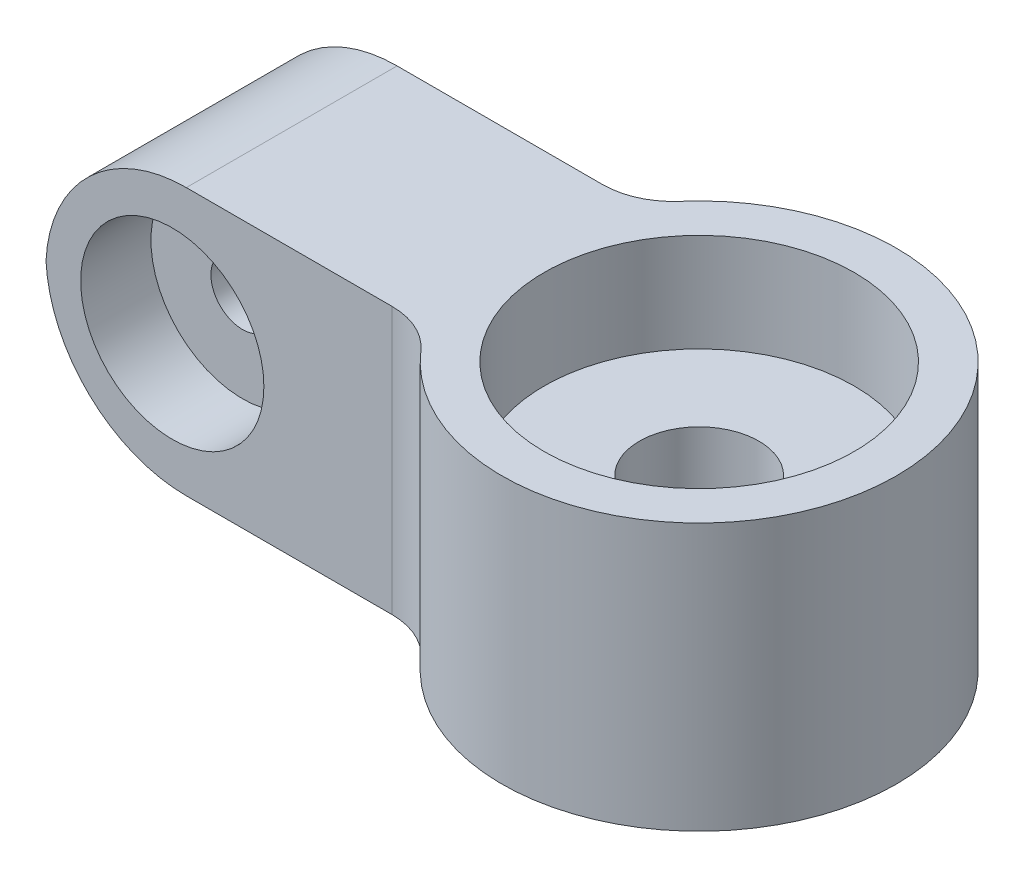
SolidWorks part; units mm, degrees
ref_plane "Front Plane" through (0, 0, 0) normal (0, 0, 1) x (1, 0, 0)
ref_plane "Top Plane" through (0, 0, 0) normal (0, 1, 0) x (1, 0, 0)
ref_plane "Right Plane" through (0, 0, 0) normal (1, 0, 0) x (0, 0, -1)
sketch "Sketch1" plane through (0, 0, 0) normal (0, 0, 1) x (1, 0, 0)
  line L0 (0, 0) -> (39, 0) construction
  line L1 (0, -9.5) -> (39, -9.5)
  line L2 (0, -9.5) -> (0, 9.5)
  line L3 (0, 9.5) -> (39, 9.5)
  line L4 (39, -9.5) -> (39, 9.5)
  circle A0 centre (9, 0) radius 6.52
  circle A1 centre (9, 0) radius 2.25
  dimension "D2" = 19
  dimension "R_625z" = 13.04
  dimension "D4" = 4.5
  dimension "D1" = 30
  dimension "D3" = 9
extrude "Boss-Extrude1" add sketch "Sketch1" along normal mid plane 15 contours A0 L0 A1 | L2 L0 A0 L4 L3 | L0 L2 L1 L4 A0 | L0 A0 A1 region at (9, 3.0122, 0) region at (9, -3.0122, 0) region at (21.8085, 5.1859, 0) region at (21.8085, -5.1859, 0)
extrude "Cortar-Extruir1" cut sketch "Sketch1<3>" against normal blind 5 from surface contours A0 starting at face at (19.5, 0, 7.5)
sketch "Sketch1<3>" plane through (0, 0, 0) normal (0, 0, 1) x (1, 0, 0) same geometry as "Sketch1"
extrude "Cortar-Extruir2" cut sketch "Sketch1<5>" along normal blind 5 from surface contours A0 starting at face at (19.5, 0, -7.5)
sketch "Sketch1<5>" plane through (0, 0, 0) normal (0, 0, 1) x (1, 0, 0) same geometry as "Sketch1"
sketch "Sketch2" plane through (0, 0, 0) normal (0, 1, 0) x (1, 0, 0)
  line L0 (39, -7.5) -> (39, 7.5) construction
  circle A0 centre (39, 0) radius 11.04
  circle A1 centre (39, 0) radius 14.04
  circle A2 centre (39, 0) radius 4.25
  dimension "D1" = 22.08
  dimension "D3" = 8.5
  dimension "D2" = 3
extrude "Boss-Extrude3" add sketch "Sketch2" against normal through all and the other way through all contours A0 | A1 A0 | A1 A0 | A0 region at (28.2723, 0, 0) region at (25.3571, 0, 0)
extrude "Cortar-Extruir3" cut sketch "Sketch2<4>" along normal blind 7 from surface contours A0 starting at face at (20.0428, -9.5, 0)
sketch "Sketch2<4>" plane through (0, 0, 0) normal (0, 1, 0) x (1, 0, 0) same geometry as "Sketch2"
extrude "Cortar-Extruir4" cut sketch "Sketch2<5>" against normal blind 7 from surface contours A0 starting at face at (41.125, 9.5, 0)
sketch "Sketch2<5>" plane through (0, 0, 0) normal (0, 1, 0) x (1, 0, 0) same geometry as "Sketch2"
extrude "Cortar-Extruir5" cut sketch "Sketch2<6>" against normal through all both and the other way through all contours A2 region at (39, 0, 0)
sketch "Sketch2<6>" plane through (0, 0, 0) normal (0, 1, 0) x (1, 0, 0) same geometry as "Sketch2"
fillet "Fillet1" radius 5 2 edges at (27.1311, 0, -7.5) (27.1311, 0, 7.5)
fillet "Fillet2" radius 10 2 edges at (0, -9.5, 0) (0, 9.5, 0)
